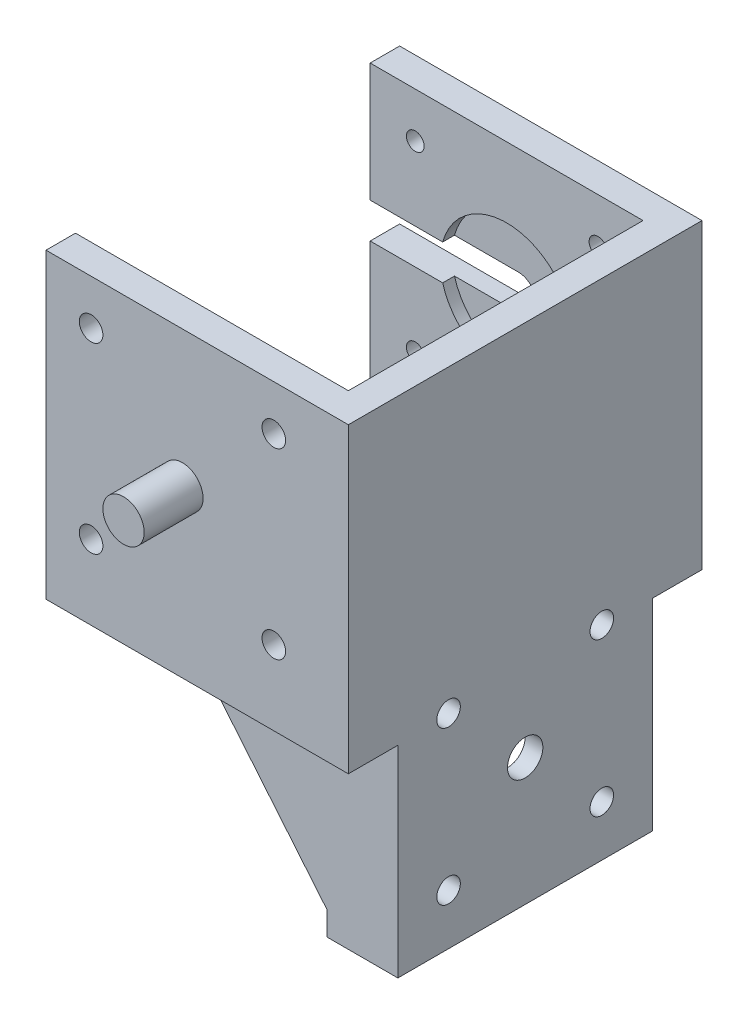
SolidWorks part; units mm, degrees
ref_plane "Front Plane" through (0, 0, 0) normal (0, 0, 1) x (1, 0, 0)
ref_plane "Top Plane" through (0, 0, 0) normal (0, 1, 0) x (1, 0, 0)
ref_plane "Right Plane" through (0, 0, 0) normal (1, 0, 0) x (0, 0, -1)
sketch "Sketch1" plane through (0, 0, 0) normal (0, 1, 0) x (1, 0, 0)
  line L0 (0, 0) -> (46.3, 0)
  line L1 (46.3, 0) -> (46.3, 50)
  line L2 (46.3, 50) -> (0, 50)
  line L3 (0, 0) -> (0, -5)
  line L4 (0, -5) -> (51.3, -5)
  line L5 (51.3, -5) -> (51.3, 55)
  line L6 (51.3, 55) -> (0, 55)
  line L7 (0, 55) -> (0, 50)
  dimension "D1" = 46.3
  dimension "D2" = 50
  dimension "D3" = 46.3
  dimension "D4" = 5
  dimension "D5" = 51.3
  dimension "D6" = 60
extrude "Boss-Extrude1" add sketch "Sketch1" along normal blind 46.3
sketch "Sketch3" plane through (0, 0, -50) normal (0, 0, 1) x (1, 0, 0)
  line L0 (23.15, 46.3) -> (23.15, 0)
  line L1 (0, 46.3) -> (46.3, 46.3) construction
  line L2 (0, 0) -> (46.3, 0) construction
  line L4 (38.65, 38.65) -> (7.65, 38.65)
  line L5 (38.65, 38.65) -> (38.65, 7.65)
  line L6 (38.65, 7.65) -> (7.65, 7.65)
  line L7 (7.65, 38.65) -> (7.65, 7.65)
  line L8 (38.65, 38.65) -> (7.65, 7.65) construction
  line L9 (38.65, 7.65) -> (7.65, 38.65) construction
  circle A0 centre (38.65, 38.65) radius 1.5
  circle A1 centre (7.65, 38.65) radius 1.5
  circle A2 centre (7.65, 7.65) radius 1.5
  circle A3 centre (38.65, 7.65) radius 1.5
  circle A4 centre (23.15, 23.15) radius 3
  circle A5 centre (23.15, 23.15) radius 11.25
  point P6 (23.15, 23.15)
  dimension "D2" = 3
  dimension "D3" = 3
  dimension "D4" = 3
  dimension "D5" = 3
  dimension "D6" = 6
  dimension "D7" = 22.5
  dimension "D1" = 31
extrude "Cut-Extrude2" cut sketch "Sketch3" against normal blind 2 contours A5
extrude "Cut-Extrude3" cut sketch "Sketch3<5>" against normal up to surface (5 mm away) contours A3 | A0 | A2 | A1 | A4 up to face at (25.65, 23.15, -55)
sketch "Sketch3<5>" plane through (0, 0, -50) normal (0, 0, 1) x (1, 0, 0) same geometry as "Sketch3"
sketch "Sketch4" plane through (0, 0, 0) normal (0, 0, -1) x (-1, 0, 0)
  line L0 (-23.15, 0) -> (-23.15, 46.3)
  line L1 (-46.3, 0) -> (0, 0) construction
  line L2 (-46.3, 46.3) -> (0, 46.3) construction
  line L4 (-7.65, 38.65) -> (-38.65, 38.65)
  line L5 (-7.65, 38.65) -> (-7.65, 7.65)
  line L6 (-7.65, 7.65) -> (-38.65, 7.65)
  line L7 (-38.65, 38.65) -> (-38.65, 7.65)
  line L8 (-7.65, 38.65) -> (-38.65, 7.65) construction
  line L9 (-7.65, 7.65) -> (-38.65, 38.65) construction
  circle A0 centre (-7.65, 7.65) radius 2
  circle A1 centre (-7.65, 38.65) radius 2
  circle A2 centre (-38.65, 7.65) radius 2
  circle A3 centre (-38.65, 38.65) radius 2
  point P6 (-23.15, 23.15)
  dimension "D2" = 4
  dimension "D3" = 4
  dimension "D4" = 4
  dimension "D5" = 4
  dimension "D1" = 31
extrude "Cut-Extrude4" cut sketch "Sketch4" against normal up to surface (5 mm away) contours A1 | A3 | A2 | A0 up to face at (25.65, 23.15, 5)
sketch "Sketch5" plane through (0, 0, 0) normal (0, -1, 0) x (1, 0, 0)
  line L0 (46.3, -7.4) -> (46.3, -42.6)
  line L1 (46.3, -50) -> (46.3, 0) construction
  line L2 (46.3, -42.6) -> (51.3, -42.6)
  line L4 (51.3, 5) -> (51.3, -55) construction
  line L5 (51.3, -42.6) -> (51.3, -7.4)
  line L6 (51.3, -7.4) -> (46.3, -7.4)
  dimension "D1" = 35.2
  dimension "D2" = 35.2
extrude "Boss-Extrude2" add sketch "Sketch5" along normal blind 35.2
sketch "Sketch6" plane through (51.3, 0, 0) normal (1, 0, 0) x (0, 0, -1)
  line L0 (7.4, 0) -> (3.4, 0)
  line L1 (-5, 0) -> (7.4, 0) construction
  line L2 (3.4, 0) -> (3.4, -39.2)
  line L3 (3.4, -39.2) -> (46.6, -39.2)
  line L4 (46.6, -39.2) -> (46.6, 0)
  line L5 (42.6, 0) -> (55, 0) construction
  line L6 (46.6, 0) -> (42.6, 0)
  line L7 (42.6, 0) -> (42.6, -35.2)
  line L8 (42.6, -35.2) -> (7.4, -35.2)
  line L9 (7.4, -35.2) -> (7.4, 0)
  dimension "D1" = 4
  dimension "D2" = 39.2
  dimension "D3" = 43.2
extrude "Boss-Extrude4" add sketch "Sketch6" against normal blind 12 contours L4 L6 L7 L8 L9 L0 L2 L3
sketch "Sketch8" plane through (46.3, 0, 0) normal (-1, 0, 0) x (0, 0, 1)
  line L0 (-42.6, -17.6) -> (-7.4, -17.6)
  line L1 (-42.6, 0) -> (-42.6, -35.2) construction
  line L2 (-7.4, -35.2) -> (-7.4, 0) construction
  line L4 (-38, -4.6) -> (-12, -4.6)
  line L5 (-38, -4.6) -> (-38, -30.6)
  line L6 (-38, -30.6) -> (-12, -30.6)
  line L7 (-12, -4.6) -> (-12, -30.6)
  line L8 (-38, -4.6) -> (-12, -30.6) construction
  line L9 (-38, -30.6) -> (-12, -4.6) construction
  circle A0 centre (-12, -4.6) radius 2
  circle A1 centre (-38, -4.6) radius 2
  circle A2 centre (-38, -30.6) radius 2
  circle A3 centre (-12, -30.6) radius 2
  circle A4 centre (-25, -17.6) radius 11
  circle A5 centre (-25, -17.6) radius 3
  point P6 (-25, -17.6)
  dimension "D2" = 4
  dimension "D3" = 4
  dimension "D4" = 4
  dimension "D5" = 4
  dimension "D6" = 22
  dimension "D7" = 6
  dimension "D1" = 26
extrude "Cut-Extrude5" cut sketch "Sketch8" against normal up to surface (5 mm away) contours A3 | A2 | A0 | A1 | A5 up to face at (51.3, 1.775, -25)
extrude "Cut-Extrude6" cut sketch "Sketch8<3>" against normal blind 2 contours A4
sketch "Sketch8<3>" plane through (46.3, 0, 0) normal (-1, 0, 0) x (0, 0, 1) same geometry as "Sketch8"
sketch "Sketch10" plane through (0, 0, 0) normal (0, -1, 0) x (1, 0, 0)
  line L0 (51.3, 5) -> (51.3, -7.4)
  line L1 (51.3, -3.4) -> (51.3, -46.6) construction
  line L2 (51.3, -7.4) -> (0, -7.4)
  line L3 (0, -7.4) -> (0, 5)
  line L4 (0, 5) -> (51.3, 5)
  dimension "D1" = 12.4
extrude "Boss-Extrude8" add sketch "Sketch10" along normal blind 5
sketch "Sketch11" plane through (0, 0, 0) normal (0, -1, 0) x (1, 0, 0)
  line L0 (51.3, -55) -> (51.3, -42.6)
  line L1 (51.3, -42.6) -> (0, -42.6)
  line L2 (0, -42.6) -> (0, -55)
  line L3 (0, -55) -> (51.3, -55)
  dimension "D1" = 12.4
extrude "Boss-Extrude9" add sketch "Sketch11" along normal blind 5
sketch "Sketch12" plane through (0, 0, -42.6) normal (0, 0, 1) x (1, 0, 0)
  line L0 (39.3, -5) -> (14.3, -5)
  line L1 (39.3, -5) -> (0, -5) construction
  line L2 (14.3, -5) -> (39.3, -35.2)
  line L3 (39.3, -5) -> (39.3, -35.2) construction
  line L4 (39.3, -35.2) -> (39.3, -5)
  dimension "D1" = 25
extrude "Boss-Extrude10" add sketch "Sketch12" against normal blind 4
sketch "Sketch13" plane through (0, 0, -7.4) normal (0, 0, -1) x (-1, 0, 0)
  line L0 (-39.3, -5) -> (-14.3, -5)
  line L1 (0, -5) -> (-39.3, -5) construction
  line L2 (-14.3, -5) -> (-39.3, -35.2)
  line L3 (-39.3, -35.2) -> (-39.3, -5)
  dimension "D1" = 25
extrude "Boss-Extrude11" add sketch "Sketch13" against normal blind 4
sketch "Sketch15" plane through (0, 0, -55) normal (0, 0, -1) x (-1, 0, 0)
  line L0 (-23.15, 26.15) -> (0, 26.15)
  line L1 (0, 46.3) -> (0, -5) construction
  line L2 (-23.15, 26.15) -> (-23.15, 20.15)
  line L3 (-23.15, 20.15) -> (0, 20.15)
  line L4 (0, 20.15) -> (0, 26.15)
  circle A0 centre (-23.15, 23.15) radius 3 construction
extrude "Cut-Extrude7" cut sketch "Sketch15" against normal up to surface (5 mm away) up to face at (40.15, 38.65, -50)
sketch "Sketch18" plane through (0, 0, 0) normal (0, 0, -1) x (-1, 0, 0)
  line L0 (-23.15, 46.3) -> (-23.15, 0)
  line L1 (-46.3, 46.3) -> (0, 46.3) construction
  line L2 (-46.3, 0) -> (0, 0) construction
  circle A0 centre (-23.15, 23.15) radius 3.5
  dimension "D1" = 7
extrude "Boss-Extrude12" add sketch "Sketch18" against normal blind 15 contours A0
